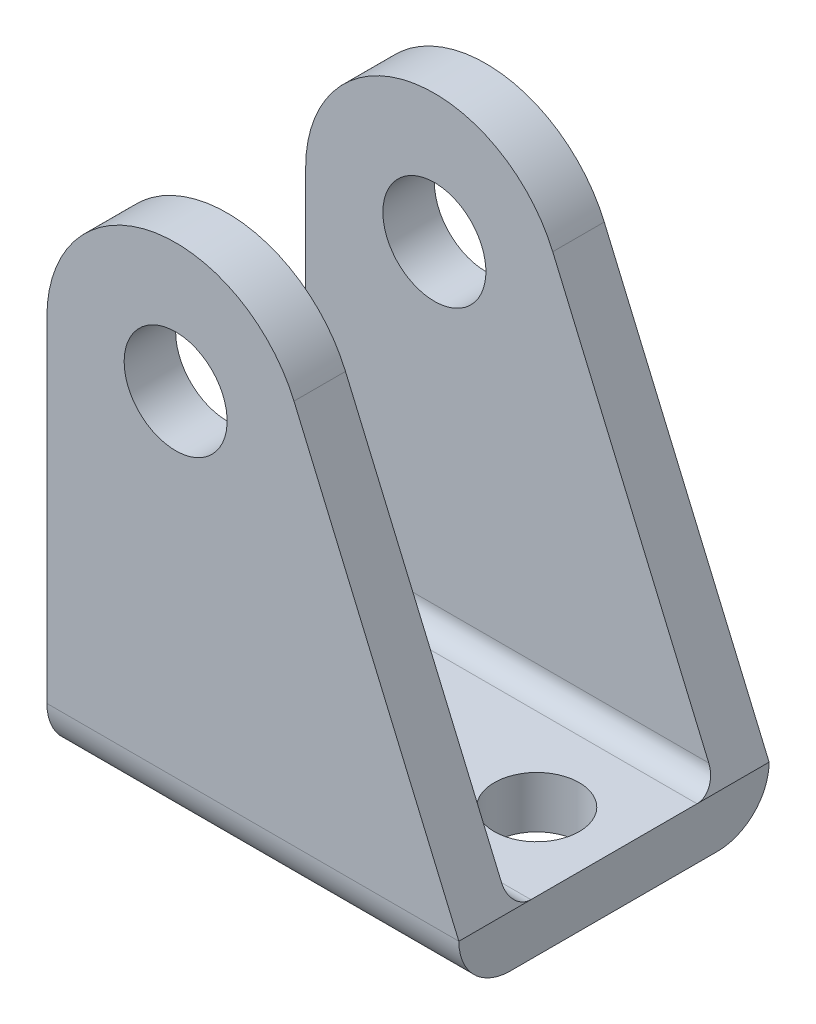
SolidWorks part; units mm, degrees
ref_plane "Front Plane" through (0, 0, 0) normal (0, 0, 1) x (1, 0, 0)
ref_plane "Top Plane" through (0, 0, 0) normal (0, 1, 0) x (1, 0, 0)
ref_plane "Right Plane" through (0, 0, 0) normal (1, 0, 0) x (0, 0, -1)
ref_plane "Plane1" through (0, 0, 0) normal (1, 0, 0) x (0, 0, -1)
sketch "Sketch1" plane through (0, 0, 0) normal (1, 0, 0) x (0, 0, -1)
  line L0 (-8.05, 0) -> (8.05, 0)
  line L1 (12.05, 4) -> (12.05, 40)
  line L2 (12.05, 40) -> (8.05, 40)
  line L3 (8.05, 40) -> (8.05, 5.6)
  line L4 (6.45, 4) -> (-6.45, 4)
  line L5 (-8.05, 5.6) -> (-8.05, 40)
  line L6 (-8.05, 40) -> (-12.05, 40)
  line L7 (-12.05, 40) -> (-12.05, 4)
  arc A0 (-12.05, 4) -> (-8.05, 0) centre (-8.05, 4) ccw
  arc A1 (8.05, 0) -> (12.05, 4) centre (8.05, 4) ccw
  arc A2 (8.05, 5.6) -> (6.45, 4) centre (6.45, 5.6) cw
  arc A3 (-6.45, 4) -> (-8.05, 5.6) centre (-6.45, 5.6) cw
extrude "Boss-Extrude1" add sketch "Sketch1" against normal blind 32 and the other way blind 32
ref_plane "Plane2" through (0, 0, 0) normal (0, 0, 1) x (1, 0, 0)
sketch "Sketch2" plane through (0, 0, 0) normal (0, 0, 1) x (1, 0, 0)
  line L0 (-48.1, 60) -> (-48.1, -16.1)
  line L1 (-48.1, -16.1) -> (48.1, -16.1)
  line L2 (48.1, -16.1) -> (48.1, 60)
  line L3 (48.1, 60) -> (-48.1, 60)
  line L4 (0, 30) -> (0, 0)
  line L5 (0, 0) -> (32, 0)
  line L6 (32, 0) -> (32, 4)
  line L7 (32, 4) -> (19.194, 33.9333)
  arc A0 (19.194, 33.9333) -> (0, 30) centre (10, 30) ccw
extrude "Cut-Extrude1" cut sketch "Sketch2" against normal blind 32 and the other way blind 32
ref_plane "Plane3" through (0, 0, 0) normal (0, 0, 1) x (1, 0, 0)
sketch "Sketch3" plane through (0, 0, 0) normal (0, 0, 1) x (1, 0, 0)
  circle A0 centre (10, 30) radius 4
extrude "Cut-Extrude2" cut sketch "Sketch3" against normal blind 16.1 and the other way blind 16.1
ref_plane "Plane4" through (0, 0, 0) normal (0, 1, 0) x (1, 0, 0)
sketch "Sketch4" plane through (0, 0, 0) normal (0, 1, 0) x (1, 0, 0)
  circle A0 centre (6, 0) radius 3.3
extrude "Cut-Extrude3" cut sketch "Sketch4" against normal blind 4 and the other way blind 4
ref_plane "Plane5" through (0, 0, 0) normal (0, 1, 0) x (1, 0, 0)
sketch "Sketch5" plane through (0, 0, 0) normal (0, 1, 0) x (1, 0, 0)
  circle A0 centre (26, 0) radius 3.3
extrude "Cut-Extrude4" cut sketch "Sketch5" against normal blind 4 and the other way blind 4
